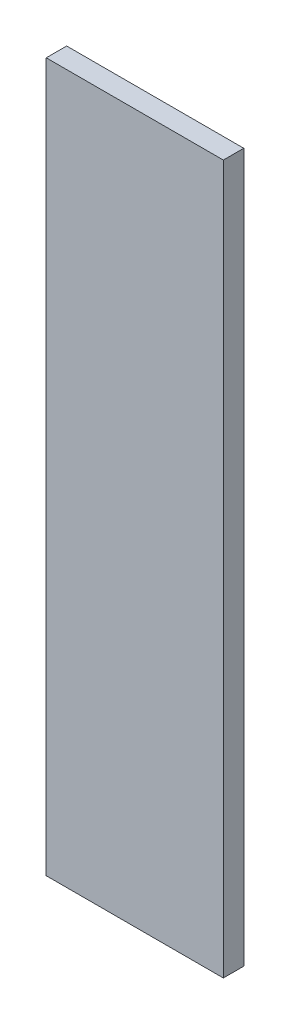
SolidWorks part; units mm, degrees
ref_plane "Front Plane" through (0, 0, 0) normal (0, 0, 1) x (1, 0, 0)
ref_plane "Top Plane" through (0, 0, 0) normal (0, 1, 0) x (1, 0, 0)
ref_plane "Right Plane" through (0, 0, 0) normal (1, 0, 0) x (0, 0, -1)
sketch "Sketch1" plane through (0, 0, 0) normal (0, 0, 1) x (1, 0, 0)
  line L1 (-49.2574, 89.9404) -> (115.8426, 89.9404)
  line L2 (-49.2574, 89.9404) -> (-49.2574, -570.4596)
  line L3 (-49.2574, -570.4596) -> (115.8426, -570.4596)
  line L4 (115.8426, 89.9404) -> (115.8426, -570.4596)
  line L5 (-49.2574, 89.9404) -> (115.8426, -570.4596) construction
  line L6 (-49.2574, -570.4596) -> (115.8426, 89.9404) construction
  point P0 (33.2926, -240.2596)
extrude "Boss-Extrude1" add sketch "Sketch1" along normal blind 19.05 contours L2 L1 L4 L3
